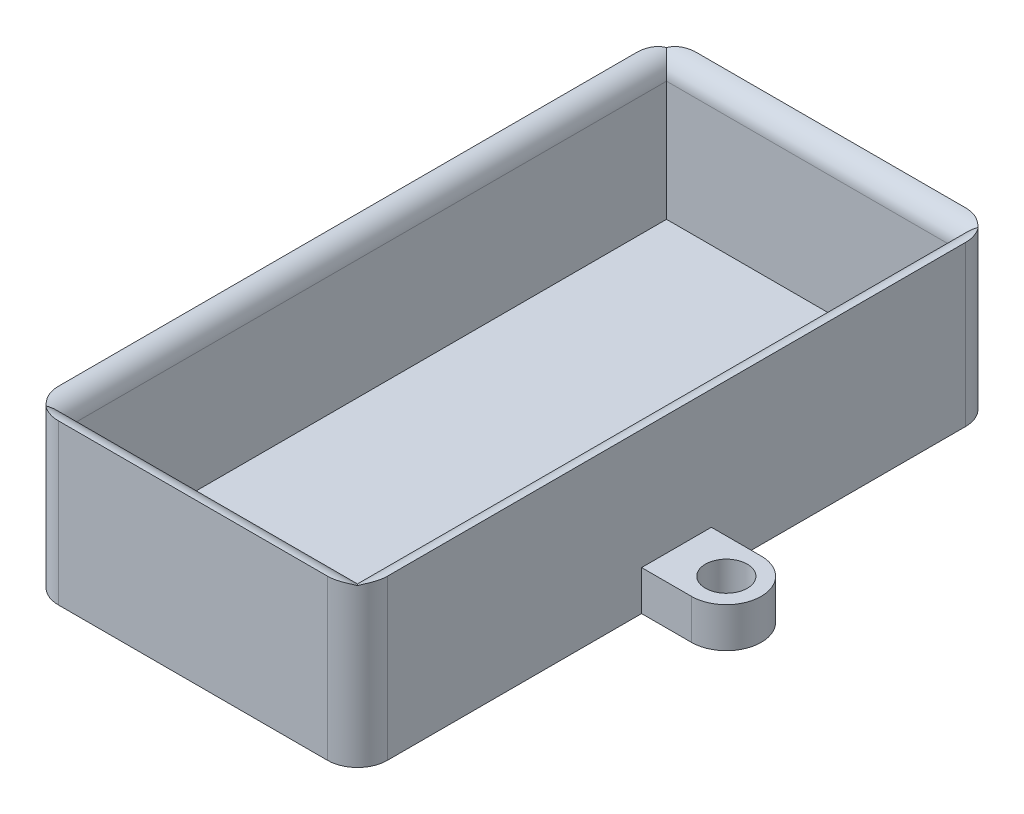
SolidWorks part; units mm, degrees
ref_plane "Front Plane" through (0, 0, 0) normal (0, 0, 1) x (1, 0, 0)
ref_plane "Top Plane" through (0, 0, 0) normal (0, 1, 0) x (1, 0, 0)
ref_plane "Right Plane" through (0, 0, 0) normal (1, 0, 0) x (0, 0, -1)
sketch "Sketch2" plane through (0, 0, 0) normal (0, 1, 0) x (1, 0, 0)
  line L1 (-14.5, 30) -> (14.5, 30)
  line L2 (-14.5, 30) -> (-14.5, -30)
  line L3 (-14.5, -30) -> (14.5, -30)
  line L4 (14.5, 30) -> (14.5, -30)
  line L5 (-14.5, 30) -> (14.5, -30) construction
  line L6 (-14.5, -30) -> (14.5, 30) construction
  line L7 (-16.5, 32) -> (16.5, 32)
  line L8 (-16.5, 32) -> (-16.5, -32)
  line L9 (-16.5, -32) -> (16.5, -32)
  line L10 (16.5, 32) -> (16.5, -32)
  line L11 (-16.5, 32) -> (16.5, -32) construction
  line L12 (-16.5, -32) -> (16.5, 32) construction
  point P0 (0, 0)
  point P6 (0, 0)
  dimension "D1" = 29
  dimension "D2" = 60
  dimension "D3" = 2
  dimension "D4" = 2
extrude "Boss-Extrude1" add sketch "Sketch2" along normal blind 14
sketch "Sketch3" plane through (0, 0, 0) normal (0, -1, 0) x (1, 0, 0)
  line L1 (-16.5, 32) -> (16.5, 32)
  line L2 (-16.5, 32) -> (-16.5, -32)
  line L3 (-16.5, -32) -> (16.5, -32)
  line L4 (16.5, 32) -> (16.5, -32)
extrude "Boss-Extrude2" add sketch "Sketch3" along normal blind 2
sketch "Sketch4" plane through (0, -2, 0) normal (0, -1, 0) x (1, 0, 0)
  line L0 (0, 32) -> (0, -32) construction
  line L1 (16.5, 32) -> (-16.5, 32) construction
  line L2 (-16.5, -32) -> (16.5, -32) construction
  line L3 (-21.5, 3.5) -> (-16.5, 3.5)
  line L4 (-16.5, 32) -> (-16.5, -32) construction
  line L5 (-21.5, -3.5) -> (-16.5, -3.5)
  line L6 (-16.5, 3.5) -> (-16.5, -3.5)
  line L7 (0, 0) -> (-16.5, 0) construction
  line L8 (16.5, 3.5) -> (16.5, -3.5)
  line L9 (21.5, -3.5) -> (16.5, -3.5)
  line L10 (21.5, 3.5) -> (16.5, 3.5)
  arc A0 (-21.5, 3.5) -> (-21.5, -3.5) centre (-21.5, 0) ccw
  circle A1 centre (-21.5, 0) radius 2.1
  circle A2 centre (21.5, 0) radius 2.1
  arc A3 (21.5, 3.5) -> (21.5, -3.5) centre (21.5, 0) cw
  dimension "D1" = 3.5
  dimension "D2" = 4.2
  dimension "D3" = 5
extrude "Boss-Extrude3" add sketch "Sketch4" against normal blind 4
fillet "Fillet1" radius 3 4 edges at (16.5, 6, -32) (-16.5, 6, -32) (16.5, 6, 32) (-16.5, 6, 32)
fillet "Fillet2" radius 2 4 edges at (14.5, 14, 0) (0, 14, -30) (-14.5, 14, 0) (0, 14, 30)
